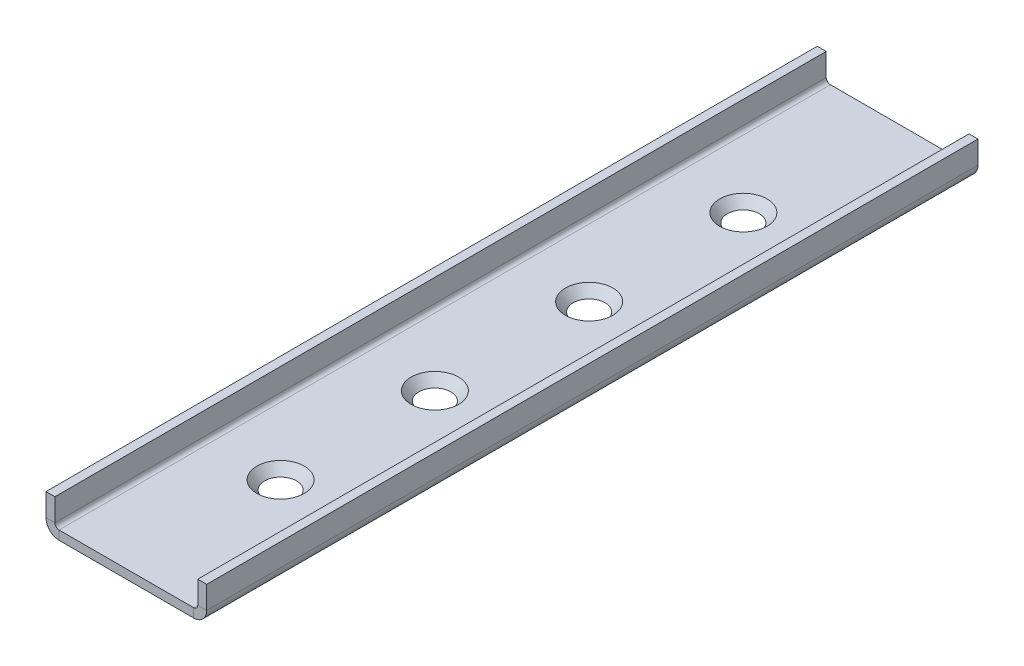
SolidWorks part; units mm, degrees
note: The reader was unsure of these and kept them because the rebuilt part matched: thickness of "Base-Flange1", "Edge-Flange1", "Sheet-Metal1", "Sheet-Metal2", "Sheet-Metal3", "Sheet-Metal4"; flange length of "Edge-Flange1".
material "1060 Alloy"
ref_plane "Front Plane" through (0, 0, 0) normal (0, 0, 1) x (1, 0, 0)
ref_plane "Top Plane" through (0, 0, 0) normal (0, 1, 0) x (1, 0, 0)
ref_plane "Right Plane" through (0, 0, 0) normal (1, 0, 0) x (0, 0, -1)
sketch "Sketch1" plane through (0, 0, 0) normal (0, 1, 0) x (1, 0, 0)
  line L1 (-14.2875, -68.58) -> (14.2875, -68.58)
  line L2 (-14.2875, -68.58) -> (-14.2875, 68.58)
  line L3 (-14.2875, 68.58) -> (14.2875, 68.58)
  line L4 (14.2875, -68.58) -> (14.2875, 68.58)
  line L5 (-14.2875, -68.58) -> (14.2875, 68.58) construction
  line L6 (-14.2875, 68.58) -> (14.2875, -68.58) construction
  point P0 (0, 0)
  dimension "D1" = 137.16
  dimension "D2" = 28.575
base flange "Base-Flange1" sketch "Sketch1" thickness 1.5875 reverse thickness direction no parameters "D1"=0.7366
ref_plane "Plane1" through (14.2875, 0, 68.58) normal (0, 0, -1) x (-1, 0, 0)
edge flange "Edge-Flange1" sketch "Sketch9" flange angle 90 flange length 6.35 flange position material inside bend radius 0.7366 thickness 1.5875 relief rectangular parameters "D6"=10
sketch "Sketch9" plane through (-14.2875, 0, 0) normal (-1, 0, 0) x (0, 0, 1)
  line L2 (-68.58, 0) -> (-68.58, 4.7625)
  line L3 (-68.58, 4.7625) -> (68.58, 4.7625)
  line L4 (68.58, 4.7625) -> (68.58, 0)
  line L7 (-68.58, 0) -> (68.58, 0) construction
  line L8 (-68.58, 0) -> (68.58, 0)
bend "EdgeBend1" bend radius 0.7366 bend angle 90 parameters "D5"=1
mirror "Mirror1" about plane through (0, 0, 0) normal (1, 0, 0) of "Edge-Flange1"
bend "MirrorBend1" bend radius 0.7366 bend angle 90 parameters "D5"=2
sketch "Sketch10" plane through (0, 0, 0) normal (0, 1, 0) x (1, 0, 0)
  line L0 (0, -68.58) -> (0, 68.58) construction
  line L1 (-11.9634, -68.58) -> (11.9634, -68.58) construction
  line L2 (11.9634, 68.58) -> (-11.9634, 68.58) construction
  point P0 (0, -41.148)
  point P1 (0, -13.716)
  point P2 (0, 13.716)
  point P3 (0, 41.148)
  dimension "D1" = 27.432
  dimension "D2" = 27.432
  dimension "D3" = 27.432
  dimension "D4" = 27.432
hole_wizard "CSK for #8 Flat Head Machine Screw1" positions "Sketch10" profile "Sketch11" countersink size "#8" standard "ANSI Inch" end condition through all
sketch "Sketch11" plane through (0, 0, 41.148) normal (1, 0, 0) x (0, 0, 1)
  line L0 (0, 0) -> (0, 1.5875)
  line L1 (0, 1.5875) -> (2.2479, 1.5875)
  line L2 (2.2479, 1.5875) -> (2.2479, 2.2645)
  line L3 (2.2479, 2.2645) -> (4.2164, 0)
  line L5 (4.2164, 0) -> (0, 0)
  line L6 (-2.2479, 2.2645) -> (-4.2164, 0) construction
  line L11 (0, -6.35) -> (0, 107.95) construction
  dimension "Thru Hole Dia." = 4.4958
  dimension "Thru Hole Depth" = 1.5875
  dimension "Near C'Sink Dia." = 8.4328
  dimension "Near C'Sink Angle" = 82
sketch "Bend-Lines1" [suppressed] plane through (0, 0, 0) normal (0, 1, 0) x (1, 0, 0)
sketch "Bounding-Box1" [suppressed] plane through (0, 0, 0) normal (0, 1, 0) x (1, 0, 0)
sheet metal parameters "Sheet-Metal1" thickness 1.5875 parameters "D1"=0.7366
flat pattern "Flat-Pattern1" [suppressed]
sketch "Bend-Lines2" plane through (0, 0, 0) normal (0, 1, 0) x (1, 0, 0)
sketch3d "Bounding-Box2" [suppressed]
  line L0 (12.7, -68.58, 0) -> (12.7, 68.58, 0) construction
  line L1 (-12.7, -68.58, 0) -> (-12.7, 68.58, 0) construction
  line L2 (12.7, -68.58, 0) -> (-12.7, -68.58, 0) construction
  line L3 (12.7, 68.58, 0) -> (-12.7, 68.58, 0) construction
sheet metal parameters "Sheet-Metal2" thickness 1.5875 parameters "D1"=0.7366, "D7"=3.175
flat pattern "Flat-Pattern1"
sketch "Bend-Lines2" plane through (0, 0, 0) normal (0, 1, 0) x (1, 0, 0)
  line L0 (-13.7887, 68.58) -> (-13.7887, -68.58) construction
  line L1 (-13.7887, 68.58) -> (-13.7887, -68.58) construction
sketch3d "Bounding-Box2" [suppressed]
  line L0 (-18.0525, -68.58, 0) -> (-18.0525, 68.58, 0) construction
  line L1 (15.875, -68.58, 0) -> (15.875, 68.58, 0) construction
  line L2 (-18.0525, -68.58, 0) -> (15.875, -68.58, 0) construction
  line L3 (-18.0525, 68.58, 0) -> (15.875, 68.58, 0) construction
bend of the flat pattern "Flatten-<EdgeBend1>1"
sheet metal parameters "Sheet-Metal3" thickness 1.5875 parameters "D1"=0.7366, "D7"=3.175
flat pattern "Flat-Pattern1"
sketch "Bend-Lines2" plane through (0, 0, 0) normal (0, 1, 0) x (1, 0, 0)
  line L0 (-14.7528, 68.58) -> (-14.7528, -68.58) construction
  line L1 (-14.7528, 68.58) -> (-14.7528, -68.58) construction
  line L2 (14.7528, -68.58) -> (14.7528, 68.58) construction
  line L3 (14.7528, -68.58) -> (14.7528, 68.58) construction
sketch3d "Bounding-Box2" [suppressed]
  line L0 (-19.9807, -68.58, 0) -> (-19.9807, 68.58, 0) construction
  line L1 (19.9807, -68.58, 0) -> (19.9807, 68.58, 0) construction
  line L2 (-19.9807, -68.58, 0) -> (19.9807, -68.58, 0) construction
  line L3 (-19.9807, 68.58, 0) -> (19.9807, 68.58, 0) construction
bend of the flat pattern "Flatten-<EdgeBend1>1"
bend of the flat pattern "Flatten-<MirrorBend1>1"
sheet metal parameters "Sheet-Metal4" thickness 1.5875 parameters "D1"=0.7366, "D7"=3.175
flat pattern "Flat-Pattern1"
sketch "Bend-Lines2" plane through (0, 0, 0) normal (0, 1, 0) x (1, 0, 0)
  line L0 (-13.1653, 68.58) -> (-13.1653, -68.58) construction
  line L1 (-13.1653, 68.58) -> (-13.1653, -68.58) construction
  line L2 (13.1653, -68.58) -> (13.1653, 68.58) construction
  line L3 (13.1653, -68.58) -> (13.1653, 68.58) construction
sketch3d "Bounding-Box2" [suppressed]
  line L0 (-18.3932, -68.58, 0) -> (-18.3932, 68.58, 0) construction
  line L1 (18.3932, -68.58, 0) -> (18.3932, 68.58, 0) construction
  line L2 (-18.3932, -68.58, 0) -> (18.3932, -68.58, 0) construction
  line L3 (-18.3932, 68.58, 0) -> (18.3932, 68.58, 0) construction
bend of the flat pattern "Flatten-<EdgeBend1>1"
bend of the flat pattern "Flatten-<MirrorBend1>1"
